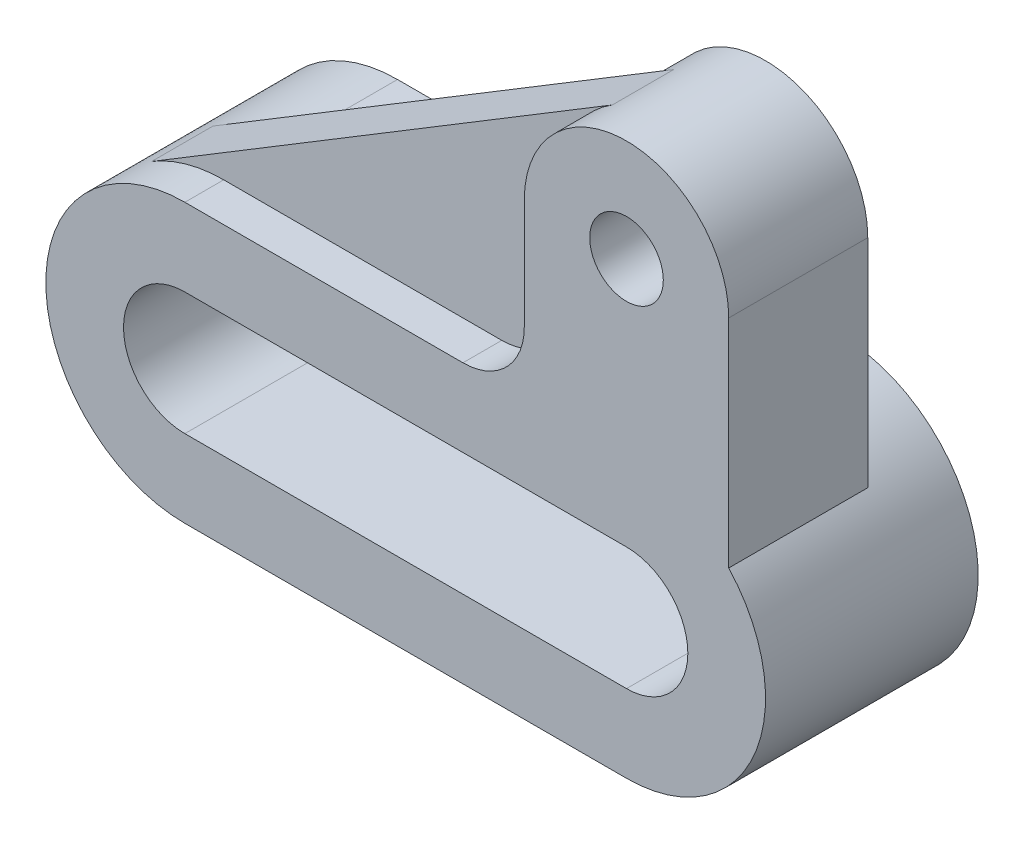
SolidWorks part; units mm, degrees
ref_plane "Front Plane" through (0, 0, 0) normal (0, 0, 1) x (1, 0, 0)
ref_plane "Top Plane" through (0, 0, 0) normal (0, 1, 0) x (1, 0, 0)
ref_plane "Right Plane" through (0, 0, 0) normal (1, 0, 0) x (0, 0, -1)
sketch "Sketch1" plane through (0, 0, 0) normal (0, 0, 1) x (1, 0, 0)
  line L0 (-54, 0) -> (54, 0) construction
  line L1 (-54, 34) -> (54, 34)
  line L2 (-54, -34) -> (54, -34)
  line L3 (-54, 0) -> (54, 0) construction
  line L4 (-54, 15) -> (54, 15)
  line L5 (-54, -15) -> (54, -15)
  arc A0 (-54, 34) -> (-54, -34) centre (-54, 0) ccw
  arc A1 (54, -34) -> (54, 34) centre (54, 0) ccw
  arc A2 (-54, 15) -> (-54, -15) centre (-54, 0) ccw
  arc A3 (54, -15) -> (54, 15) centre (54, 0) ccw
  point P2 (0, 0)
  point P9 (0, 0)
  dimension "D1" = 15
  dimension "D2" = 34
  dimension "D3" = 108
extrude "Boss-Extrude1" add sketch "Sketch1" along normal blind 52
sketch "Sketch2" plane through (0, 0, 52) normal (0, 0, 1) x (1, 0, 0)
  line L0 (29, 76) -> (29, 34)
  line L1 (54, 34) -> (-54, 34) construction
  line L2 (79, 76) -> (79, 23.0434)
  line L3 (54, 34) -> (29, 34)
  arc A0 (79, 76) -> (29, 76) centre (54, 76) ccw
  circle A1 centre (54, 76) radius 9
  arc A2 (54, -34) -> (54, 34) centre (54, 0) ccw construction
  arc A3 (79, 23.0434) -> (54, 34) centre (54, 0) ccw
  dimension "D1" = 18
  dimension "D2" = 50
  dimension "D3" = 76
  dimension "D4" = 108
extrude "Boss-Extrude2" add sketch "Sketch2" against normal blind 34 contours L0 L3 A3 L2 A0
extrude "Cut-Extrude2" cut sketch "Sketch2<3>" against normal through all contours A1
sketch "Sketch2<3>" plane through (0, 0, 52) normal (0, 0, 1) x (1, 0, 0) same geometry as "Sketch2"
fillet "Fillet1" radius 15 1 edges at (29, 34, 35)
ref_plane "Plane1" through (0, 0, 35) normal (0, 0, 1) x (1, 0, 0)
sketch "Sketch4" plane through (0, 0, 35) normal (0, 0, 1) x (1, 0, 0)
  line L0 (-71.6263, 29.0743) -> (41.0395, 97.3781)
  arc A0 (-54, 34) -> (-54, -34) centre (-54, 0) ccw construction
  arc A1 (79, 76) -> (29, 76) centre (54, 76) ccw construction
rib "Rib3" sketch "Sketch4" sketch "Sketch4" thickness 15 extrusion direction parallel to sketch draft on no parameters "D1"=15
